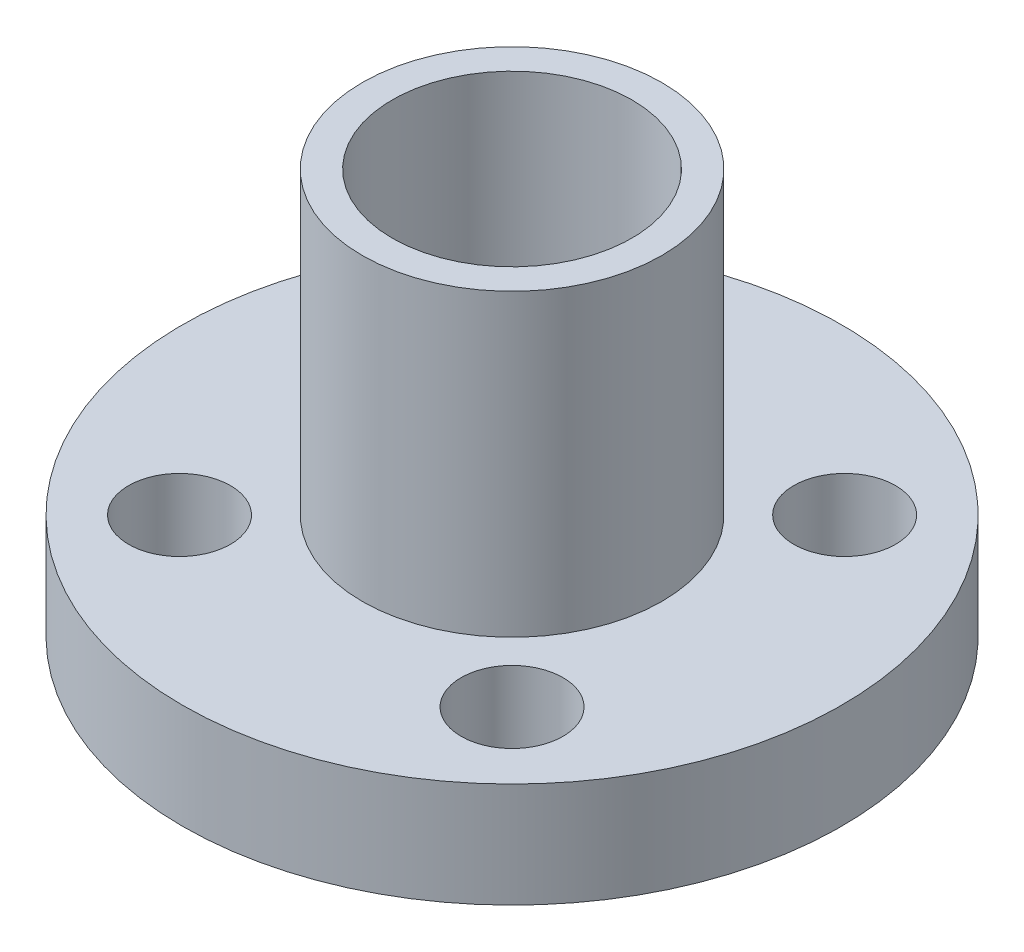
SolidWorks part; units mm, degrees
ref_plane "Front Plane" through (0, 0, 0) normal (0, 0, 1) x (1, 0, 0)
ref_plane "Top Plane" through (0, 0, 0) normal (0, 1, 0) x (1, 0, 0)
ref_plane "Right Plane" through (0, 0, 0) normal (1, 0, 0) x (0, 0, -1)
sketch "Sketch1" plane through (0, 0, 0) normal (0, 1, 0) x (1, 0, 0)
  circle A0 centre (-13.8328, -13.4035) radius 4
  circle A1 centre (-19.3828, -7.8535) radius 1.7
  circle A2 centre (-8.2828, -7.8535) radius 1.7
  circle A3 centre (-8.2828, -18.9535) radius 1.7
  circle A4 centre (-19.3828, -18.9535) radius 1.7
  circle A5 centre (-13.8328, -13.4035) radius 11
  dimension "D1" = 3.4
  dimension "D2" = 8
extrude "Boss-Extrude1" add sketch "Sketch1" along normal blind 3.5
sketch "Sketch2" plane through (0, 3.5, 0) normal (0, 1, 0) x (1, 0, 0)
  circle A0 centre (-13.8328, -13.4035) radius 5
  circle A1 centre (-13.8328, -13.4035) radius 11 construction
  dimension "D1" = 0
extrude "Boss-Extrude2" add sketch "Sketch2" along normal blind 10
extrude "Boss-Extrude3" add sketch "Sketch2<2>" against normal blind 5
sketch "Sketch2<2>" plane through (0, 3.5, 0) normal (0, 1, 0) x (1, 0, 0) same geometry as "Sketch2"
sketch "Sketch3" plane through (0, 13.5, 0) normal (0, 1, 0) x (1, 0, 0)
  circle A0 centre (-13.8328, -13.4035) radius 4
  circle A1 centre (-13.8328, -13.4035) radius 5 construction
  dimension "D1" = 0
extrude "Cut-Extrude1" cut sketch "Sketch3" against normal blind 20
